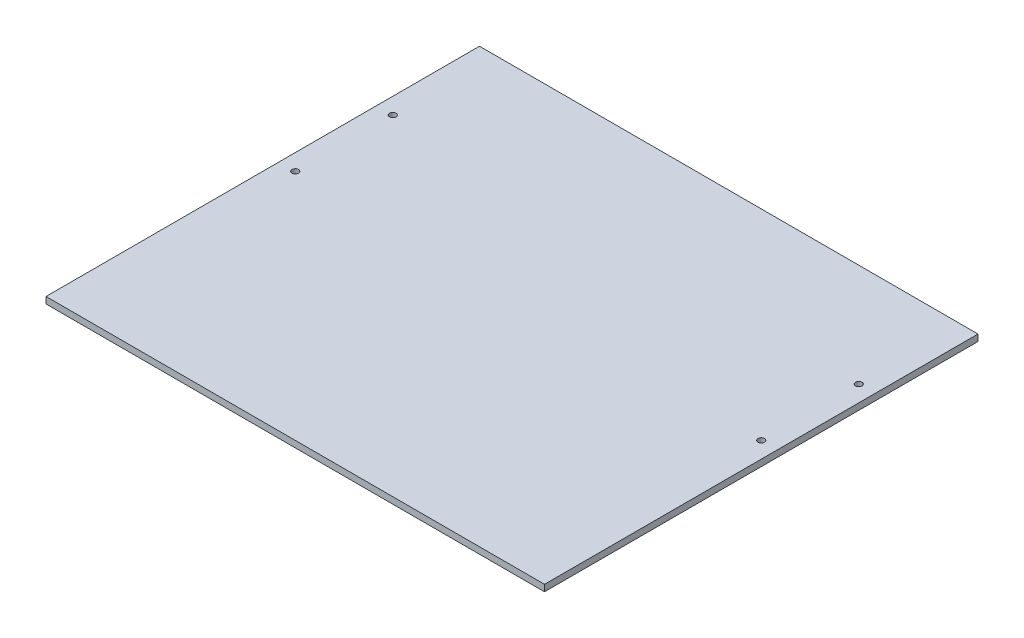
SolidWorks part; units mm, degrees
material "AISI 1045 Aço, trefilado"
ref_plane "Plano frontal" through (0, 0, 0) normal (0, 0, 1) x (1, 0, 0)
ref_plane "Plano superior" through (0, 0, 0) normal (0, 1, 0) x (1, 0, 0)
ref_plane "Plano direito" through (0, 0, 0) normal (1, 0, 0) x (0, 0, -1)
sketch "Esboço1" plane through (0, 0, 0) normal (0, 1, 0) x (1, 0, 0)
  line L0 (-107.5, 7.5) -> (-107.5, 52.5) construction
  line L1 (-115, -100) -> (115, -100)
  line L2 (-115, -100) -> (-115, 100)
  line L3 (-115, 100) -> (115, 100)
  line L4 (115, -100) -> (115, 100)
  line L5 (-115, -100) -> (115, 100) construction
  line L6 (-115, 100) -> (115, -100) construction
  line L7 (0, 100) -> (0, -100) construction
  line L8 (107.5, 7.5) -> (107.5, 52.5) construction
  circle A0 centre (-107.5, 52.5) radius 1.5
  circle A1 centre (-107.5, 7.5) radius 1.5
  circle A2 centre (107.5, 7.5) radius 1.5
  circle A3 centre (107.5, 52.5) radius 1.5
  point P0 (0, 0)
  point P13 (-107.5, 51.3549)
  point P18 (-107.5, 22.5)
  point P19 (0, 0)
  point P20 (-107.5, 30)
  dimension "D4" = 3
  dimension "D1" = 200
  dimension "D2" = 230
  dimension "D3" = 45
  dimension "D5" = 7.5
  dimension "D6" = 70
extrude "Ressalto-extrusão1" add sketch "Esboço1" along normal blind 3
